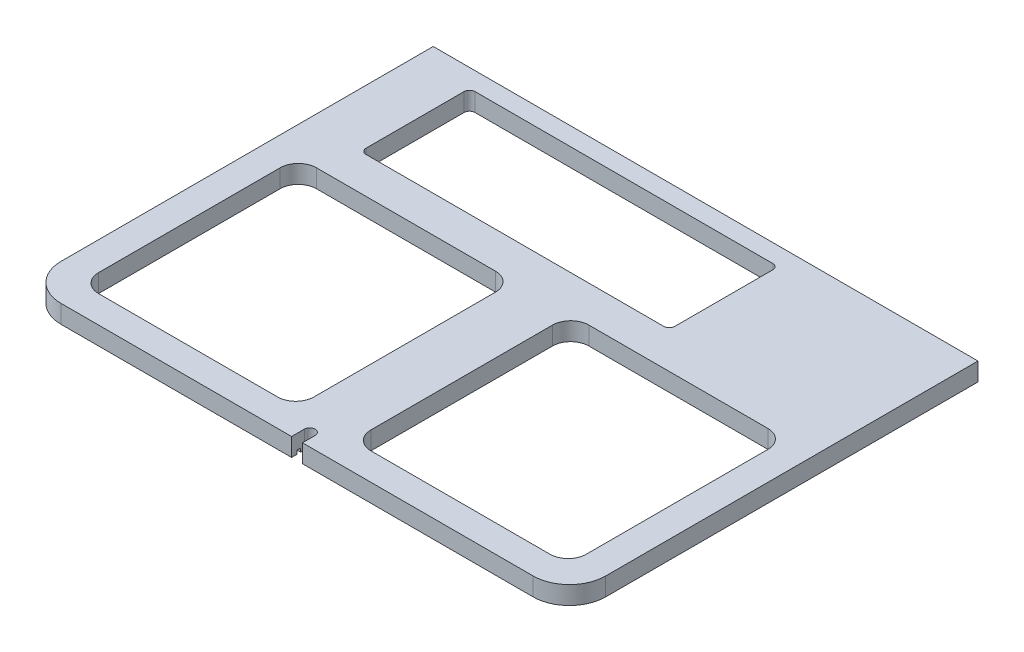
SolidWorks part; units mm, degrees
ref_plane "Ebene vorne" through (0, 0, 0) normal (0, 0, 1) x (1, 0, 0)
ref_plane "Ebene oben" through (0, 0, 0) normal (0, 1, 0) x (1, 0, 0)
ref_plane "Ebene rechts" through (0, 0, 0) normal (1, 0, 0) x (0, 0, -1)
sketch "Skizze1" plane through (0, 10, 0) normal (0, 1, 0) x (1, 0, 0)
  line L0 (0, -75) -> (130, -75)
  line L2 (0, -75) -> (0, 75.7029)
  line L3 (0, 75.7029) -> (150, 75.7029) construction
  line L4 (150, -55) -> (150, 75.7029)
  line L5 (150, -55) -> (150, 150) construction
  line L6 (15.7029, -60) -> (15.7029, -75.7029) construction
  line L7 (15.7029, 60) -> (134.2971, 60)
  line L8 (15.7029, 60) -> (15.7029, -60)
  line L9 (15.7029, -60) -> (134.2971, -60)
  line L10 (134.2971, 60) -> (134.2971, -60)
  line L11 (15.7029, -75.7029) -> (15.7029, -60) construction
  line L12 (0, -60) -> (15.7029, -60) construction
  line L13 (134.2971, 60) -> (134.2971, 75.7029) construction
  line L14 (134.2971, 60) -> (150, 60) construction
  line L15 (150, 75.7029) -> (150, 150)
  line L16 (150, 150) -> (0, 150)
  line L17 (0, 150) -> (0, 75.7029)
  arc A0 (130, -75) -> (150, -55) centre (130, -55) ccw
  arc A1 (130, -75) -> (150, -55) centre (130, -55) ccw construction
  dimension "D1" = 120
extrude "Linear austragen1" add sketch "Skizze1" along normal blind 10
fillet "Verrundung2" radius 10 4 edges at (15.7029, 15, 60) (134.2971, 15, 60) (134.2971, 15, -60) (15.7029, 15, -60)
mirror "Spiegeln1" about plane through (0, 20, -150) normal (1, 0, 0) of "Verrundung2", "Linear austragen1"
sketch "Skizze3" plane through (0, 10, 0) normal (0, -1, 0) x (1, 0, 0)
  line L0 (-150, 55) -> (-150, -150) construction
  line L1 (-120, -80) -> (50, -80)
  line L2 (-120, -80) -> (-120, -140)
  line L3 (-120, -140) -> (50, -140)
  line L4 (50, -80) -> (50, -140)
  line L5 (150, -150) -> (-150, -150) construction
  line L6 (0, -60.4164) -> (0, -150) construction
  dimension "D1" = 30
  dimension "D2" = 10
  dimension "D3" = 50
  dimension "D4" = 60
extrude "Schnitt-Linear austragen1" cut sketch "Skizze3" against normal blind 10
fillet "Verrundung3" radius 3 4 edges at (-120, 15, -140) (50, 15, -140) (50, 15, -80) (-120, 15, -80)
sketch "Skizze4" plane through (0, 10, 0) normal (0, -1, 0) x (1, 0, 0)
  line L0 (-3.0001, 75) -> (-3.0001, 68)
  line L1 (-130, 75) -> (130, 75) construction
  line L2 (-3.0001, 75) -> (2.9592, 75)
  line L3 (2.9592, 75) -> (2.9999, 68.0175)
  arc A0 (-3.0001, 68) -> (2.9999, 68.0175) centre (-0.0001, 68) ccw
  dimension "D2" = 3
  dimension "D1" = 7
extrude "Schnitt-Linear austragen2" cut sketch "Skizze4" against normal blind 10
sketch "Skizze5" plane through (0, 10, 0) normal (0, -1, 0) x (1, 0, 0)
  line L0 (-7.0204, 72) -> (-3.0001, 75) construction
  line L1 (-7.0204, 72) -> (6.9796, 72)
  line L2 (-7.0204, 72) -> (-7.0204, 70)
  line L3 (-7.0204, 70) -> (6.9796, 70)
  line L4 (6.9796, 72) -> (6.9796, 70)
  line L5 (2.9592, 75) -> (6.9796, 72) construction
  dimension "D1" = 14
  dimension "D2" = 2
  dimension "D3" = 3
extrude "Schnitt-Linear austragen3" cut sketch "Skizze5" against normal blind 2
